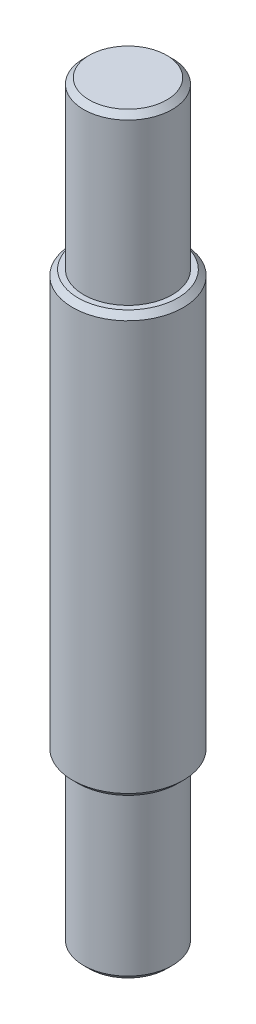
SolidWorks part; units mm, degrees
ref_plane "Front Plane" through (0, 0, 0) normal (0, 0, 1) x (1, 0, 0)
ref_plane "Top Plane" through (0, 0, 0) normal (0, 1, 0) x (1, 0, 0)
ref_plane "Right Plane" through (0, 0, 0) normal (1, 0, 0) x (0, 0, -1)
sketch "Sketch1" plane through (0, 0, 0) normal (0, 1, 0) x (1, 0, 0)
  circle A0 centre (0, 0) radius 5
  dimension "D1" = 10
extrude "Boss-Extrude1" add sketch "Sketch1" along normal mid plane 38
sketch "Sketch2" plane through (0, 19, 0) normal (0, 1, 0) x (1, 0, 0)
  circle A0 centre (0, 0) radius 4
  dimension "D1" = 8
extrude "Boss-Extrude2" add sketch "Sketch2" along normal blind 15
extrude "Boss-Extrude3" add sketch "Sketch2<2>" against normal blind 15 from surface starting at face at (0, -19, 5)
sketch "Sketch2<2>" plane through (0, 19, 0) normal (0, 1, 0) x (1, 0, 0) same geometry as "Sketch2"
chamfer "Chamfer1" distance 0.5 angle 45 2 edges at (0, -34, 4) (0, 34, 4)
chamfer "Chamfer2" distance 0.5 angle 45 2 edges at (0, 19, 5) (0, -19, 5)
